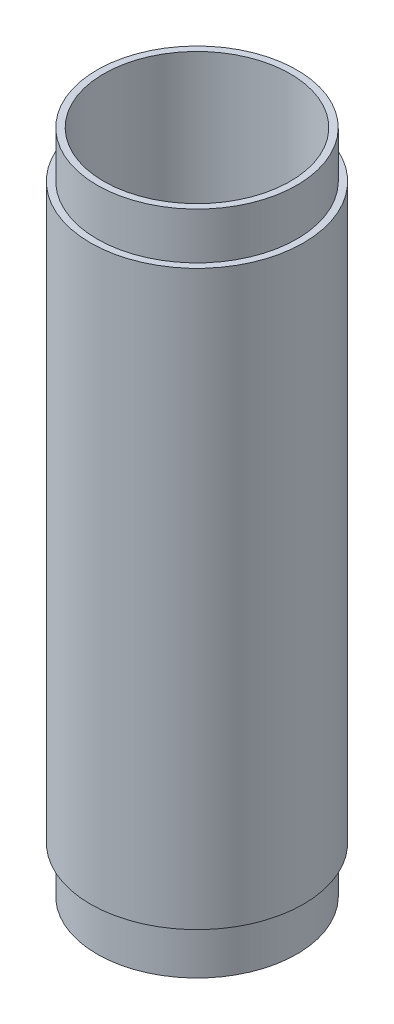
SolidWorks part; units mm, degrees
material "PET"
ref_plane "Alzado" through (0, 0, 0) normal (0, 0, 1) x (1, 0, 0)
ref_plane "Planta" through (0, 0, 0) normal (0, 1, 0) x (1, 0, 0)
ref_plane "Vista lateral" through (0, 0, 0) normal (1, 0, 0) x (0, 0, -1)
sketch "Croquis8" plane through (0, 0, 0) normal (1, 0, 0) x (0, 0, -1)
  line L0 (0, 0) -> (0, 100) construction
  line L3 (-7.0678, 7) -> (-7.0678, 93) construction
  dimension "D1" = 86
  dimension "D2" = 100
ref_plane "Plano1" through (0, 50, 0) normal (0, 1, 0) x (1, 0, 0)
sketch "Croquis9" plane through (0, 50, 0) normal (0, 1, 0) x (1, 0, 0)
  circle A0 centre (0, 0) radius 14
  circle A1 centre (0, 0) radius 16
sketch "Croquis10" plane through (0, 50, 0) normal (0, 1, 0) x (1, 0, 0)
  circle A0 centre (0, 0) radius 14
  circle A1 centre (0, 0) radius 15
extrude "Saliente-Extruir1" add sketch "Croquis10" along normal blind 50 and the other way blind 50
extrude "Saliente-Extruir2" add sketch "Croquis9" along normal blind 43 and the other way blind 43
